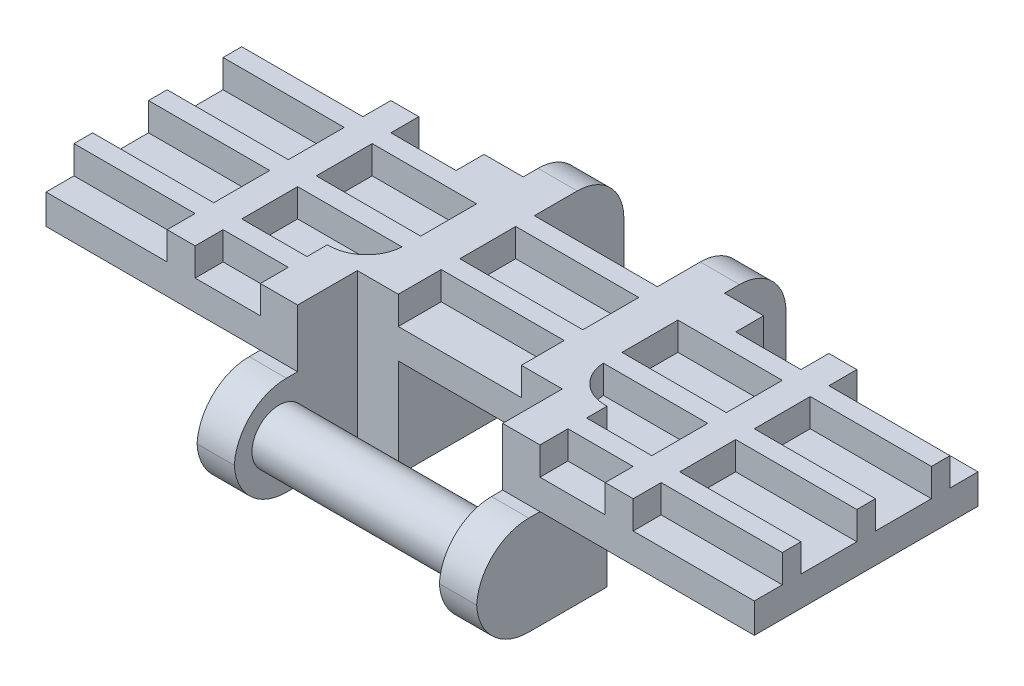
SolidWorks part; units mm, degrees
ref_plane "前视基准面" through (0, 0, 0) normal (0, 0, 1) x (1, 0, 0)
ref_plane "上视基准面" through (0, 0, 0) normal (0, 1, 0) x (1, 0, 0)
ref_plane "右视基准面" through (0, 0, 0) normal (1, 0, 0) x (0, 0, -1)
other "Configuration Table"
sketch "草图1" plane through (0, 0, 0) normal (0, 1, 0) x (1, 0, 0)
  line L1 (-19, -6) -> (19, -6)
  line L2 (-19, -6) -> (-19, 6)
  line L3 (-19, 6) -> (19, 6)
  line L4 (19, -6) -> (19, 6)
  line L5 (-19, -6) -> (19, 6) construction
  line L6 (-19, 6) -> (19, -6) construction
  line L13 (-19, 4.5) -> (19, 4.5)
  line L14 (-19, 4.5) -> (-19, 3.5)
  line L15 (-19, 3.5) -> (19, 3.5)
  line L16 (19, 4.5) -> (19, 3.5)
  line L17 (-19, 0.5) -> (19, 0.5)
  line L18 (-19, 0.5) -> (-19, -0.5)
  line L19 (-19, -0.5) -> (19, -0.5)
  line L20 (19, 0.5) -> (19, -0.5)
  line L21 (-19, -3.5) -> (19, -3.5)
  line L22 (-19, -3.5) -> (-19, -4.5)
  line L23 (-19, -4.5) -> (19, -4.5)
  line L24 (19, -3.5) -> (19, -4.5)
  line L25 (-12.5, 6) -> (-11, 6)
  line L26 (-12.5, 6) -> (-12.5, -6)
  line L27 (-12.5, -6) -> (-11, -6)
  line L28 (-11, 6) -> (-11, -6)
  line L29 (12.5, 6) -> (11, 6)
  line L30 (12.5, 6) -> (12.5, -6)
  line L31 (12.5, -6) -> (11, -6)
  line L32 (11, 6) -> (11, -6)
  point P0 (0, 0)
  point P6 (0, 0)
  dimension "D1" = 38
  dimension "D2" = 12
  dimension "D3" = 11
  dimension "D4" = 11
  dimension "D5" = 1
  dimension "D6" = 1.5
  dimension "D7" = 1.5
  dimension "D8" = 5.5
  dimension "D9" = 1.5
extrude "凸台-拉伸1" add sketch "草图1" along normal blind 1.6 contours L2 L3 L4 L1
extrude "凸台-拉伸2" add sketch "草图1<3>" along normal blind 1.5 from surface contours L13 L16 L15 L14 | L17 L20 L19 L18 | L21 L24 L23 L22 | L26 L27 L28 L25 | L30 L31 L32 L29 starting at face at (0, 1.6, 0)
sketch "草图1<3>" plane through (0, 0, 0) normal (0, 1, 0) x (1, 0, 0) same geometry as "草图1"
sketch "草图2" plane through (0, 0, 0) normal (0, 1, 0) x (1, 0, 0)
  line L0 (0, 0) -> (0, -13.8005) construction
  line L1 (-5.4, 9.3) -> (5.4, 9.3)
  line L2 (-5.4, 9.3) -> (-5.4, -2.8)
  line L3 (-5.4, -2.8) -> (5.4, -2.8)
  line L4 (5.4, 9.3) -> (5.4, -2.8)
  line L5 (-7.5, -2.8) -> (7.5, -2.8)
  line L6 (11, 4.5) -> (-11, 4.5) construction
  line L7 (-7.5, 6) -> (-5.4, 6)
  line L8 (-3.3, 9.3) -> (3.3, 9.3)
  line L9 (-3.3, 9.3) -> (-3.3, -2.8)
  line L10 (-3.3, -2.8) -> (3.3, -2.8)
  line L11 (3.3, 9.3) -> (3.3, -2.8)
  line L16 (-11, -6) -> (11, -6) construction
  line L17 (-11, 6) -> (11, 6) construction
  line L18 (-5.5, -2.4) -> (-5.5, -9.4)
  line L19 (-7.5, -2.4) -> (7.5, -2.4)
  line L20 (-7.5, -2.4) -> (-7.5, -9.4)
  line L21 (-7.5, -9.4) -> (7.5, -9.4)
  line L22 (7.5, -2.4) -> (7.5, -9.4)
  line L23 (5.5, -2.4) -> (5.5, -9.4)
  line L24 (-7.5, 6) -> (-7.5, 4.5)
  line L25 (-7.5, 4.5) -> (-5.4, 4.5)
  line L26 (-5.4, 6) -> (-5.4, 4.5)
  line L27 (7.5, 6) -> (5.4, 6)
  line L28 (7.5, 6) -> (7.5, 4.5)
  line L29 (7.5, 4.5) -> (5.4, 4.5)
  line L30 (5.4, 6) -> (5.4, 4.5)
  point P5 (0, -2.8)
  point P15 (0, 9.3)
  point P20 (0, -9.4)
  dimension "D1" = 10.8
  dimension "D2" = 3.2
  dimension "D3" = 6.6
  dimension "D4" = 3.3
  dimension "D5" = 15
  dimension "D6" = 2
  dimension "D7" = 2
  dimension "D8" = 3.4
  dimension "D9" = 7
extrude "凸台-拉伸3" add sketch "草图2" against normal blind 8.4 from surface contours L1 L11 L3 L4 | L9 L1 L2 L3 | L20 L21 L18 L19 | L19 L23 L21 L22 | L19 L18 L5 L2 | L19 L20 L5 L18 | L19 L2 L3 L9 | L19 L11 L3 L4 | L23 L19 L4 L5 | L19 L23 L5 L22 region at (-4.35, 0, -3.45) region at (4.35, 0, -3.45) region at (-4.35, 0, 2.6) region at (4.35, 0, 2.6) region at (-5.45, 0, 2.6) region at (5.45, 0, 2.6) region at (-6.5, 0, 2.6) region at (6.5, 0, 2.6) region at (-6.5, 0, 6.1) region at (6.5, 0, 6.1) starting at face at (0, 3.1, 0)
extrude "凸台-拉伸5" add sketch "草图2<4>" along normal up to surface (3.1 mm away) contours L27 L30 L29 L28 | L7 L26 L25 L24 up to face at (0, 3.1, -2)
sketch "草图2<4>" plane through (0, 0, 0) normal (0, 1, 0) x (1, 0, 0) same geometry as "草图2"
extrude "切除-拉伸1" cut sketch "草图2<3>" along normal through all contours L0 L5 L3 L18 L21 | L10 L0 L21 L23 L5 L3 region at (2.75, 0, 6.1) region at (-2.75, 0, 6.1)
sketch "草图2<3>" plane through (0, 0, 0) normal (0, 1, 0) x (1, 0, 0) same geometry as "草图2"
fillet "圆角1" radius 3 2 edges at (5.4, -2.65, 2.4) (-5.4, -2.65, 2.4)
sketch "草图3" plane through (-5.5, 0, 0) normal (1, 0, 0) x (0, 0, -1)
  line L2 (-7, -2.5) -> (5.58, -2.5)
  line L3 (2.8, -4.1) -> (9.3, -4.1)
  line L4 (2.8, -4.1) -> (2.8, -5.3)
  line L5 (2.8, -5.3) -> (9.3, -5.3)
  line L6 (9.3, -4.1) -> (9.3, -5.3)
  line L7 (-9.4, -5.3) -> (-9.4, 3.1) construction
  line L8 (-6, 3.1) -> (-9.4, 3.1)
  line L9 (-6, 3.1) -> (-6, 0)
  line L10 (-6, 0) -> (-9.4, 0)
  line L11 (-9.4, 3.1) -> (-9.4, 0)
  circle A0 centre (-7, -2.5) radius 1.45
  circle A1 centre (5.58, -2.5) radius 1.8
  dimension "D1" = 2.9
  dimension "D3" = 3.6
  dimension "D7" = 7
  dimension "D2" = 2.5
  dimension "D4" = 1.2
  dimension "D5" = 6.5
  dimension "D6" = 12.58
extrude "凸台-拉伸4" add sketch "草图3" along normal up to next contours A0
extrude "切除-拉伸2" cut sketch "草图3<3>" along normal through all both and the other way through all contours L3 L6 L5 L4 | A1 | L11 L10 L9 L8
sketch "草图3<3>" plane through (-5.5, 0, 0) normal (1, 0, 0) x (0, 0, -1) same geometry as "草图3"
fillet "圆角2" radius 2.8 4 edges at (6.5, -5.3, 9.4) (-6.5, -5.3, 9.4) (-6.5, 0, 9.4) (6.5, 0, 9.4)
fillet "圆角3" radius 2.5 2 edges at (-4.35, 3.1, -9.3) (4.35, 3.1, -9.3)
fillet "圆角4" radius 1 2 edges at (-4.35, -4.1, -9.3) (4.35, -4.1, -9.3)
fillet "圆角5" radius 0.3 4 edges at (-4.35, -4.1, -6.4046) (4.35, -4.1, -6.4046) (4.35, -4.1, -4.7554) (-4.35, -4.1, -4.7554)
fillet "圆角6" radius 2 2 edges at (5.4, 2.35, 2.4) (-5.4, 2.35, 2.4)
